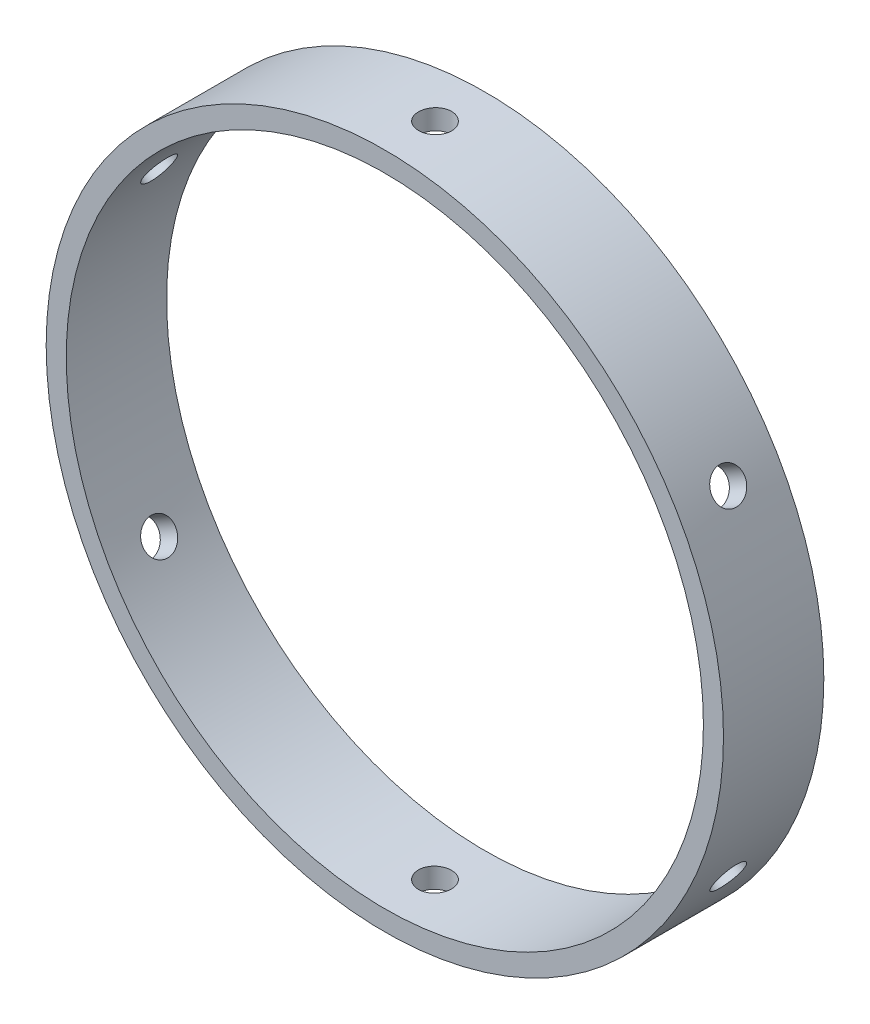
SolidWorks part; units mm, degrees
ref_plane "Front Plane" through (0, 0, 0) normal (0, 0, 1) x (1, 0, 0)
ref_plane "Top Plane" through (0, 0, 0) normal (0, 1, 0) x (1, 0, 0)
ref_plane "Right Plane" through (0, 0, 0) normal (1, 0, 0) x (0, 0, -1)
sketch "Sketch1" plane through (0, 0, 0) normal (0, 0, 1) x (1, 0, 0)
  line L0 (0, 31.75) -> (0, 33.75) construction
  circle A0 centre (0, 0) radius 31.75
  circle A1 centre (0, 0) radius 33.75
  dimension "D1" = 63.5
  dimension "D2" = 2
extrude "Boss-Extrude1" add sketch "Sketch1" along normal mid plane 10
sketch "Sketch2" plane through (0, 0, 0) normal (0, 1, 0) x (1, 0, 0)
  point P0 (0, 0)
hole_wizard "M4x0.7 Tapped Hole1" positions "Sketch2" profile "Sketch3" tap size "M4x0.7" standard "ANSI Metric" end condition through all
sketch "Sketch3" plane through (0, 0, 0) normal (1, 0, 0) x (0, 0, -1)
  line L0 (0, 0) -> (0, 33.75)
  line L1 (0, 33.75) -> (1.65, 33.75)
  line L2 (1.65, 33.75) -> (1.65, 0)
  line L5 (1.65, 0) -> (0, 0)
  line L11 (0, -6.35) -> (0, 107.95) construction
  dimension "Thru Tap Drill Dia." = 3.3
  dimension "Thru Tap Drill Depth" = 33.75
cosmetic thread "Hole Thread1" parameters "D2"=4
pattern_circular "CirPattern1" count 6 over 360 about axis through (0, 0, 5) along (0, 0, -1) of "M4x0.7 Tapped Hole1" reverse direction yes
cosmetic thread "Hole Thread2" parameters "D2"=4
cosmetic thread "Hole Thread3" parameters "D2"=4
cosmetic thread "Hole Thread4" parameters "D2"=4
cosmetic thread "Hole Thread5" parameters "D2"=4
cosmetic thread "Hole Thread6" parameters "D2"=4
